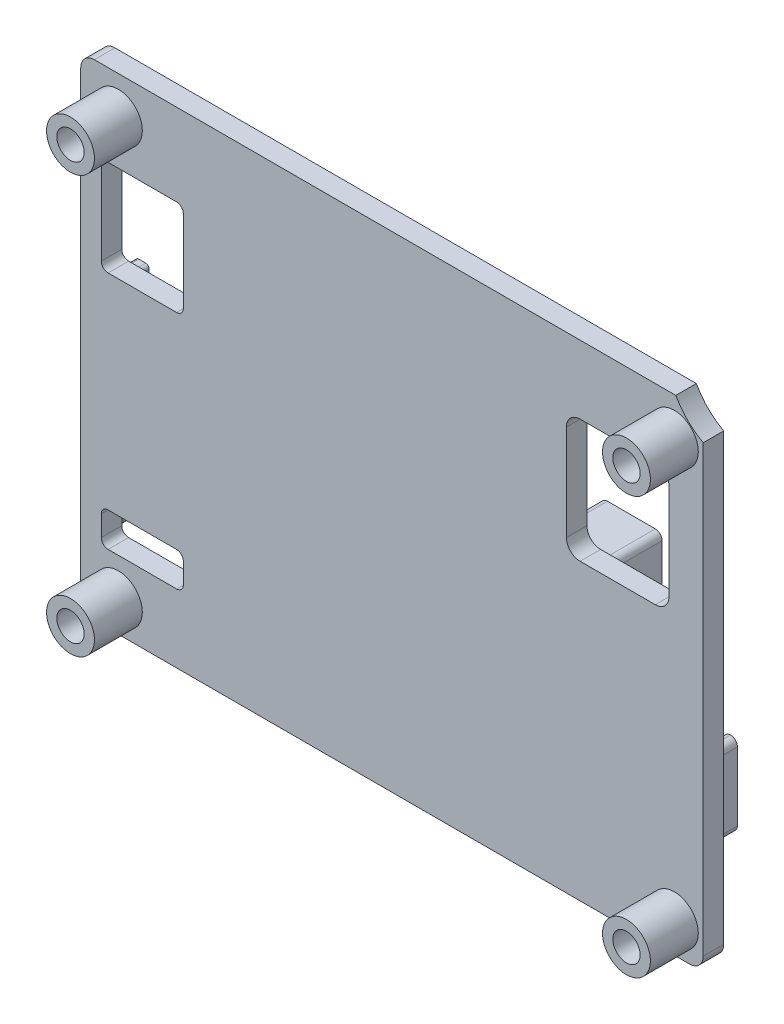
SolidWorks part; units mm, degrees
ref_plane "Front Plane" through (0, 0, 0) normal (0, 0, 1) x (1, 0, 0)
ref_plane "Top Plane" through (0, 0, 0) normal (0, 1, 0) x (1, 0, 0)
ref_plane "Right Plane" through (0, 0, 0) normal (1, 0, 0) x (0, 0, -1)
sketch "Sketch1" plane through (0, 0, 0) normal (0, 0, 1) x (1, 0, 0)
  line L1 (45.5, -35.5) -> (-45.5, -35.5)
  line L2 (45.5, -35.5) -> (45.5, 35.5)
  line L3 (45.5, 35.5) -> (-45.5, 35.5)
  line L4 (-45.5, -35.5) -> (-45.5, 35.5)
  line L5 (45.5, -35.5) -> (-45.5, 35.5) construction
  line L6 (45.5, 35.5) -> (-45.5, -35.5) construction
  point P0 (0, 0)
  dimension "D1" = 71
  dimension "D2" = 91
extrude "Boss-Extrude1" add sketch "Sketch1" along normal blind 3
sketch "Sketch3" plane through (0, 0, 0) normal (0, 0, -1) x (-1, 0, 0)
  line L1 (-45.5, 35.5) -> (-41.5, 35.5)
  line L2 (-45.5, 35.5) -> (-45.5, 31.5)
  line L3 (-45.5, 31.5) -> (-41.5, 31.5)
  line L4 (-41.5, 35.5) -> (-41.5, 31.5)
  line L5 (45.5, -35.5) -> (41.5, -35.5)
  line L6 (45.5, -35.5) -> (45.5, -31.5)
  line L7 (45.5, -31.5) -> (41.5, -31.5)
  line L8 (41.5, -35.5) -> (41.5, -31.5)
  dimension "D1" = 4
  dimension "D2" = 4
  dimension "D3" = 4
  dimension "D4" = 4
extrude "Cut-Extrude1" cut sketch "Sketch3" against normal blind 5
fillet "Fillet2" radius 10 2 edges at (-41.5, -31.5, 1.5) (41.5, 31.5, 1.5)
fillet "Fillet3" radius 2 2 edges at (45.5, -35.5, 1.5) (-45.5, 35.5, 1.5)
sketch "Sketch4" plane through (0, 0, 3) normal (0, 0, 1) x (1, 0, 0)
  line L0 (45.5, -33.5) -> (45.5, 31.5) construction
  line L1 (25.5, 25.5) -> (40.5, 25.5)
  line L2 (25.5, 25.5) -> (25.5, 7.5)
  line L3 (25.5, 7.5) -> (40.5, 7.5)
  line L4 (40.5, 25.5) -> (40.5, 7.5)
  line L5 (41.5, 35.5) -> (-43.5, 35.5) construction
  dimension "D1" = 15
  dimension "D2" = 18
  dimension "D3" = 10
  dimension "D4" = 5
extrude "Cut-Extrude2" cut sketch "Sketch4" against normal blind 5
sketch "Sketch5" plane through (0, 0, 3) normal (0, 0, 1) x (1, 0, 0)
  line L0 (-45.5, 33.5) -> (-45.5, -31.5) construction
  line L1 (41.5, 35.5) -> (-43.5, 35.5) construction
  circle A0 centre (-40, 30) radius 3.5
  circle A1 centre (-40, 30) radius 2
  dimension "D1" = 7
  dimension "D4" = 4
  dimension "D2" = 5.5
  dimension "D3" = 5.5
extrude "Boss-Extrude2" add sketch "Sketch5" along normal blind 7
pattern_linear "LPattern1" count 2 spacing 81.28 along (1, 0, 0) count 2 spacing 60.96 along (0, -1, 0) of "Boss-Extrude2"
fillet "Fillet4" radius 2 4 edges at (40.5, 7.5, 1.5) (40.5, 25.5, 1.5) (25.5, 7.5, 1.5) (25.5, 25.5, 1.5)
sketch "Sketch7" plane through (0, 0, 0) normal (0, 0, -1) x (-1, 0, 0)
  line L0 (-24.5, 2.1) -> (-18.5, 2.1)
  line L1 (-24.5, -20.5) -> (-27.5, -20.5)
  line L2 (-24.5, -20.5) -> (-24.5, 2.1)
  line L7 (-27.5, 5.1) -> (-18.5, 5.1)
  line L8 (-18.5, 2.1) -> (-18.5, 5.1)
  line L9 (-27.5, 5.1) -> (-27.5, -20.5)
  line L10 (-45.5, -33.5) -> (-45.5, 31.5) construction
  line L11 (41.5, -35.5) -> (-43.5, -35.5) construction
  dimension "D1" = 6
  dimension "D2" = 21
  dimension "D3" = 3
  dimension "D4" = 3
  dimension "D5" = 37.6
  dimension "D6" = 15
extrude "Boss-Extrude4" add sketch "Sketch7" along normal blind 9
ref_plane "Plane6" through (-0.5, 0, 0) normal (1, 0, 0) x (0, 0, -1)
mirror "Mirror1" about plane through (-0.5, 0, 0) normal (1, 0, 0) of "Boss-Extrude4"
fillet "Fillet5" radius 1 12 edges at (-25.5, 2.1, -4.5) (-19.5, 2.1, -4.5) (-19.5, 5.1, -4.5) (-28.5, 5.1, -4.5) (-28.5, -20.5, -4.5) (-25.5, -20.5, -4.5) (24.5, -20.5, -4.5) (27.5, -20.5, -4.5) (27.5, 5.1, -4.5) (18.5, 5.1, -4.5) (18.5, 2.1, -4.5) (24.5, 2.1, -4.5)
sketch "Sketch8" plane through (0, 0, 0) normal (0, 0, -1) x (-1, 0, 0)
  line L0 (-40.5, -11.5) -> (-40.5, -21.5)
  line L1 (-42.5, -11.5) -> (-40.5, -11.5)
  line L2 (-42.5, -11.5) -> (-42.5, -23.5)
  line L5 (-40.5, -21.5) -> (-36.5, -21.5)
  line L6 (-36.5, -21.5) -> (-36.5, -23.5)
  line L7 (-42.5, -23.5) -> (-36.5, -23.5)
  line L8 (-27.5, 4.1) -> (-27.5, -19.5) construction
  line L9 (41.5, -35.5) -> (-43.5, -35.5) construction
  point P8 (-41.5, -11.5)
  dimension "D1" = 13
  dimension "D2" = 2
  dimension "D3" = 12
  dimension "D4" = 2
  dimension "D5" = 12
  dimension "D6" = 4
extrude "Boss-Extrude5" add sketch "Sketch8" along normal blind 5
fillet "Fillet6" radius 1 6 edges at (40.5, -11.5, -2.5) (40.5, -21.5, -2.5) (42.5, -11.5, -2.5) (42.5, -23.5, -2.5) (36.5, -23.5, -2.5) (36.5, -21.5, -2.5)
sketch "Sketch9" plane through (0, 0, 0) normal (0, 0, -1) x (-1, 0, 0)
  line L0 (-41.5, 35.5) -> (43.5, 35.5) construction
  line L1 (0.5, 15.3) -> (25.5, 15.3)
  line L2 (0.5, 15.3) -> (0.5, 12.3)
  line L3 (0.5, 12.3) -> (25.5, 12.3)
  line L4 (25.5, 15.3) -> (25.5, 12.3)
  line L5 (45.5, 33.5) -> (45.5, -31.5) construction
  point P6 (25.5, 13.8)
  dimension "D1" = 20.2
  dimension "D2" = 20
  dimension "D3" = 25
  dimension "D4" = 3
  dimension "D5" = 3
extrude "Boss-Extrude6" add sketch "Sketch9" along normal blind 7
fillet "Fillet7" radius 1 4 edges at (-0.5, 15.3, -3.5) (-0.5, 12.3, -3.5) (-25.5, 15.3, -3.5) (-25.5, 12.3, -3.5)
sketch "Sketch10" plane through (0, 0, 0) normal (0, 0, -1) x (-1, 0, 0)
  line L0 (45.5, 33.5) -> (45.5, -31.5) construction
  line L1 (30.5, 23.5) -> (42.5, 23.5)
  line L2 (30.5, 23.5) -> (30.5, 9.5)
  line L3 (30.5, 9.5) -> (42.5, 9.5)
  line L4 (42.5, 23.5) -> (42.5, 9.5)
  line L5 (-41.5, 35.5) -> (43.5, 35.5) construction
  dimension "D1" = 12
  dimension "D2" = 3
  dimension "D3" = 14
  dimension "D4" = 12
extrude "Cut-Extrude3" cut sketch "Sketch10" against normal blind 5
fillet "Fillet8" radius 1 4 edges at (-30.5, 9.5, 1.5) (-42.5, 9.5, 1.5) (-30.5, 23.5, 1.5) (-42.5, 23.5, 1.5)
sketch "Sketch11" plane through (0, 0, 0) normal (0, 0, -1) x (-1, 0, 0)
  line L0 (41.5, -35.5) -> (-43.5, -35.5) construction
  line L1 (30.5, -20.5) -> (42.5, -20.5)
  line L2 (30.5, -20.5) -> (30.5, -25.5)
  line L3 (30.5, -25.5) -> (42.5, -25.5)
  line L4 (42.5, -20.5) -> (42.5, -25.5)
  line L12 (45.5, 33.5) -> (45.5, -31.5) construction
  dimension "D1" = 12
  dimension "D2" = 3
  dimension "D3" = 5
  dimension "D4" = 10
extrude "Cut-Extrude4" cut sketch "Sketch11" against normal up to next
fillet "Fillet9" radius 1 4 edges at (-42.5, -25.5, 1.5) (-42.5, -20.5, 1.5) (-30.5, -25.5, 1.5) (-30.5, -20.5, 1.5)
sketch "Sketch12" plane through (0, 0, 0) normal (0, 0, -1) x (-1, 0, 0)
  line L0 (45.5, 33.5) -> (45.5, -31.5) construction
  line L1 (43.5, -25.5) -> (45.5, -25.5)
  line L2 (43.5, -25.5) -> (43.5, 5.5)
  line L3 (43.5, 5.5) -> (45.5, 5.5)
  line L4 (45.5, -25.5) -> (45.5, 5.5)
  line L5 (28.5, 4.1) -> (28.5, -19.5) construction
  line L6 (41.5, -35.5) -> (-43.5, -35.5) construction
  point P9 (44.5, 5.5)
  dimension "D1" = 15
  dimension "D2" = 15
  dimension "D3" = 31
  dimension "D4" = 10
extrude "Boss-Extrude7" add sketch "Sketch12" along normal blind 5
fillet "Fillet10" radius 0.5 4 edges at (-43.5, 5.5, -2.5) (-45.5, 5.5, -2.5) (-45.5, -25.5, -2.5) (-43.5, -25.5, -2.5)
